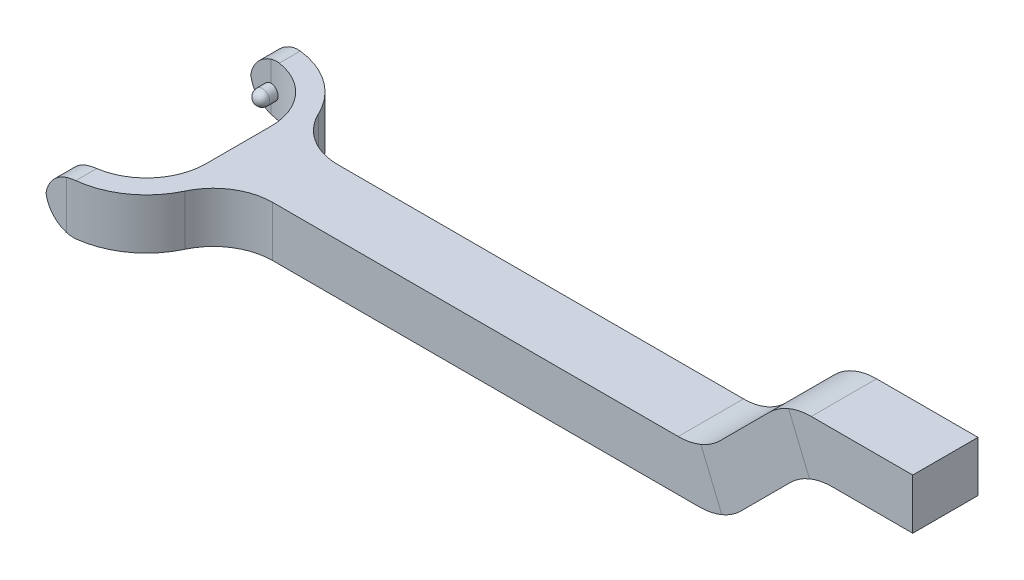
SolidWorks part; units mm, degrees
ref_plane "Front Plane" through (0, 0, 0) normal (0, 0, 1) x (1, 0, 0)
ref_plane "Top Plane" through (0, 0, 0) normal (0, 1, 0) x (1, 0, 0)
ref_plane "Right Plane" through (0, 0, 0) normal (1, 0, 0) x (0, 0, -1)
sketch "Sketch1" plane through (0, 0, 0) normal (1, 0, 0) x (0, 0, -1)
  line L1 (0, 0) -> (11, 0)
  line L2 (0, 0) -> (0, -8.5)
  line L3 (0, -8.5) -> (11, -8.5)
  line L4 (11, 0) -> (11, -8.5)
  dimension "D1" = 11
  dimension "D2" = 8.5
extrude "Boss-Extrude1" add sketch "Sketch1" along normal blind 75
ref_plane "Plane2" through (0, -4.25, 0) normal (0, 1, 0) x (1, 0, 0)
sketch3d "3DSketch3"
  line L0 (75, -3, -5.5) -> (85, -3, -5.5)
  line L1 (85, -3, -5.5) -> (99.1421, 11.1421, -5.5)
  line L2 (75, 0, -11) -> (75, 0, 0) construction
  line L3 (75, -8.5, -11) -> (75, 0, -11) construction
  line L4 (99.1421, 11.1421, -5.5) -> (119.1421, 11.1421, -5.5)
  dimension "D1" = 3
  dimension "D2" = 0
  dimension "D3" = 5.5
  dimension "D4" = 135
  dimension "D5" = 10
  dimension "D6" = 20
  dimension "D7" = 20
sketch "Sketch14" plane through (75, 0, 0) normal (1, 0, 0) x (0, 0, -1)
  line L1 (0, 0) -> (11, 0)
  line L2 (0, 0) -> (0, -8.5)
  line L3 (0, -8.5) -> (11, -8.5)
  line L4 (11, 0) -> (11, -8.5)
sweep "Sweep3" add profiles "Sketch14" path "3DSketch3"
fillet "Fillet1" radius 10 4 edges at (87.2782, -8.5, -5.5) (101.4203, 5.6421, -5.5) (97.8995, 14.1421, -5.5) (83.7574, 0, -5.5)
sketch "Sketch17" plane through (0, 0, 0) normal (0, 1, 0) x (1, 0, 0)
  line L0 (-10, -10) -> (-13.5, -10)
  line L1 (-13.5, -10) -> (-13.5, -13.5)
  line L2 (-13.5, -13.5) -> (-10, -13.5)
  line L4 (-23.4629, 5.5) -> (20.4079, 5.5) construction
  line L5 (79.6152, 0) -> (0, 0) construction
  line L20 (3.5, 0) -> (3.5, 11)
  line L22 (-13.5, 24.5) -> (-10, 24.5)
  line L23 (0, 0) -> (0, 11)
  line L24 (-13.5, 21) -> (-13.5, 24.5)
  line L25 (-10, 21) -> (-13.5, 21)
  arc A0 (-10, -10) -> (0, 0) centre (-10, 0) ccw
  arc A2 (-10, -13.5) -> (3.5, 0) centre (-10, 0) ccw
  arc A3 (-10, 24.5) -> (3.5, 11) centre (-10, 11) cw
  arc A4 (-10, 21) -> (0, 11) centre (-10, 11) cw
  dimension "D3" = 20
  dimension "D6" = 3.5
  dimension "D1" = 0
  dimension "D2" = 10
  dimension "D5" = 3.5
  dimension "D7" = 5.5
extrude "Boss-Extrude3" add sketch "Sketch17" along normal blind 8.5 from offset 8.5 offset against normal yes
fillet "Fillet5" radius 10 2 edges at (3.5, -4.25, 0) (3.5, -4.25, -11)
fillet "Fillet6" radius 5 4 edges at (-13.5, 0, 11.75) (-13.5, -8.5, 11.75) (-13.5, -8.5, -22.75) (-13.5, 0, -22.75)
sketch "Sketch18" plane through (0, 0, -21) normal (0, 0, 1) x (1, 0, 0)
  line L2 (-10, -0.2303) -> (-10, -8.2697) construction
  line L3 (0, 0) -> (-8.5, 0) construction
  circle A0 centre (-10, -5) radius 1.25
  dimension "D1" = 2.5
  dimension "D2" = 0
  dimension "D3" = 5
extrude "Boss-Extrude4" add sketch "Sketch18" along normal blind 1.5
sketch "Sketch19" plane through (0, 0, 10) normal (0, 0, -1) x (-1, 0, 0)
  line L0 (10, -0.2303) -> (10, -8.2697) construction
  circle A0 centre (10, -3.5) radius 1.25
  dimension "D1" = 2.5
  dimension "D2" = 5
extrude "Boss-Extrude5" add sketch "Sketch19" along normal blind 1.5
ref_plane "CenterOfClips" through (-7.5, 0, 0) normal (-1, 0, 0) x (0, 0, 1)
sketch "Sketch24" plane through (0, 0, 8.5) normal (0, 0, -1) x (-1, 0, 0)
  line L0 (10, -2.25) -> (10, -4.75)
  circle A0 centre (10, -3.5) radius 1.25 construction
  arc A1 (10, -4.75) -> (10, -2.25) centre (10, -3.5) ccw
revolve "Revolve9" add sketch "Sketch24" angle 180 about L0
sketch "Sketch25" plane through (0, 0, -19.5) normal (0, 0, 1) x (1, 0, 0)
  line L0 (-10, -3.75) -> (-10, -6.25)
  circle A0 centre (-10, -5) radius 1.25 construction
  arc A1 (-10, -3.75) -> (-10, -6.25) centre (-10, -5) ccw
revolve "Revolve10" add sketch "Sketch25" angle 180 about L0 reverse direction yes
